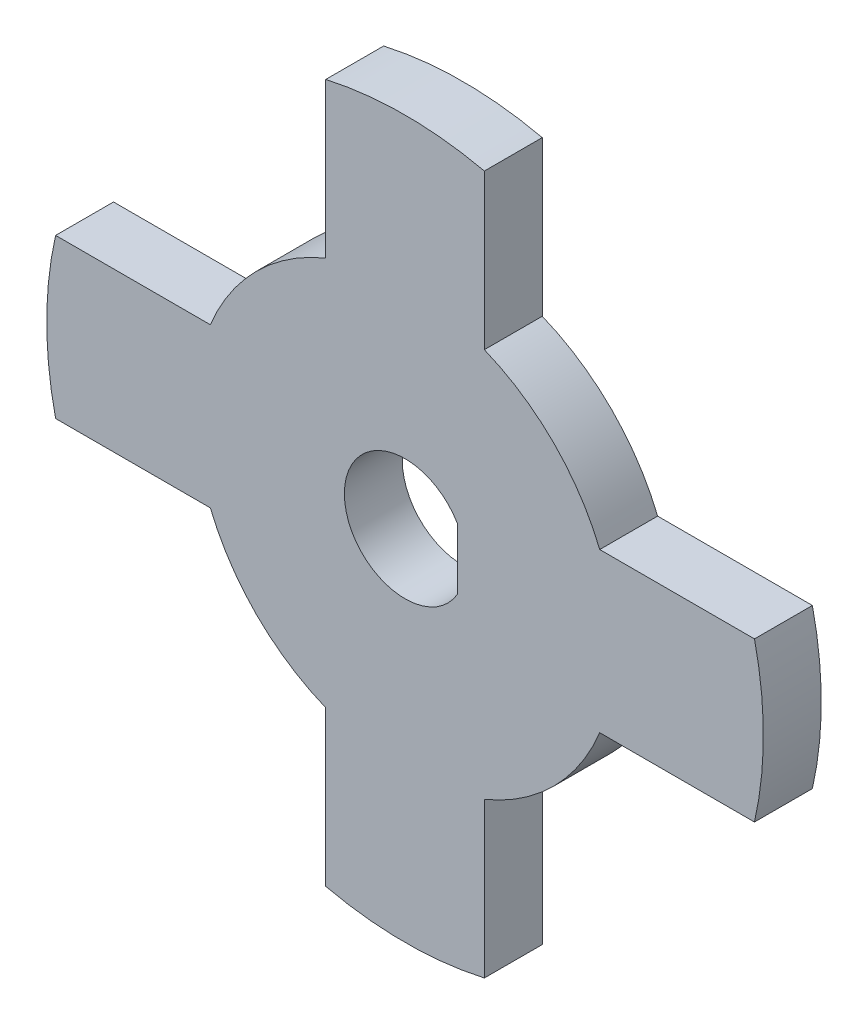
SolidWorks part; units mm, degrees
ref_plane "Front Plane" through (0, 0, 0) normal (0, 0, 1) x (1, 0, 0)
ref_plane "Top Plane" through (0, 0, 0) normal (0, 1, 0) x (1, 0, 0)
ref_plane "Right Plane" through (0, 0, 0) normal (1, 0, 0) x (0, 0, -1)
sketch "Sketch3" plane through (0, 0, 0) normal (0, 0, 1) x (1, 0, 0)
  line L0 (2.7496, 1.5875) -> (2.7496, -1.5875)
  line L1 (0, 0) -> (0, 20.2676) construction
  line L2 (4.15, 18.285) -> (4.15, 10.1871)
  line L3 (-4.15, 18.285) -> (-4.15, 10.1871)
  line L4 (18.285, -4.15) -> (10.1871, -4.15)
  line L5 (18.285, 4.15) -> (10.1871, 4.15)
  line L6 (-4.15, -18.285) -> (-4.15, -10.1871)
  line L7 (4.15, -18.285) -> (4.15, -10.1871)
  line L8 (-18.285, 4.15) -> (-10.1871, 4.15)
  line L9 (-18.285, -4.15) -> (-10.1871, -4.15)
  arc A0 (2.7496, 1.5875) -> (2.7496, -1.5875) centre (0, 0) ccw
  arc A1 (4.15, 18.285) -> (-4.15, 18.285) centre (0, 0) ccw
  arc A2 (10.1871, 4.15) -> (4.15, 10.1871) centre (0, 0) ccw
  arc A3 (-18.285, 4.15) -> (-18.285, -4.15) centre (0, 0) ccw
  arc A4 (18.285, -4.15) -> (18.285, 4.15) centre (0, 0) ccw
  arc A5 (-4.15, 10.1871) -> (-10.1871, 4.15) centre (0, 0) ccw
  arc A6 (-10.1871, -4.15) -> (-4.15, -10.1871) centre (0, 0) ccw
  arc A7 (4.15, -10.1871) -> (10.1871, -4.15) centre (0, 0) ccw
  arc A8 (-4.15, -18.285) -> (4.15, -18.285) centre (0, 0) ccw
  point P26 (0, 0)
  dimension "D1" = 6.35
  dimension "D3" = 37.5
  dimension "D4" = 22
  dimension "D2" = 3.175
  dimension "D5" = 4
  dimension "D6" = 8.3
extrude "Boss-Extrude1" add sketch "Sketch3" along normal blind 3.03
